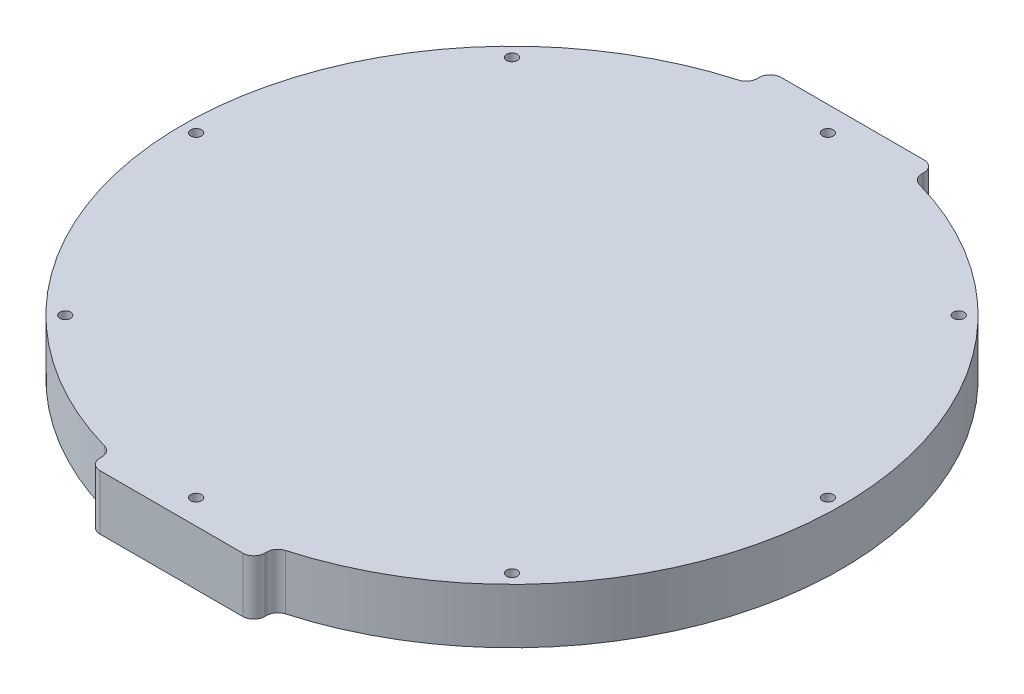
SolidWorks part; units mm, degrees
material "6061 Alloy"
ref_plane "Front Plane" through (0, 0, 0) normal (0, 0, 1) x (1, 0, 0)
ref_plane "Top Plane" through (0, 0, 0) normal (0, 1, 0) x (1, 0, 0)
ref_plane "Right Plane" through (0, 0, 0) normal (1, 0, 0) x (0, 0, -1)
sketch "Sketch2" plane through (0, 0, 0) normal (0, 1, 0) x (1, 0, 0)
  circle A0 centre (0, 0) radius 76.2
extrude "Boss-Extrude1" add sketch "Sketch2" along normal blind 12.7
sketch "Sketch3" plane through (0, 0, 0) normal (0, 0, 1) x (1, 0, 0)
  line L0 (0, 0) -> (-19.05, 0)
  line L1 (-19.05, 0) -> (-19.05, 12.7)
  line L2 (-19.05, 12.7) -> (19.05, 12.7)
  line L3 (19.05, 12.7) -> (19.05, 0)
  line L4 (0, 0) -> (19.05, 0)
extrude "Boss-Extrude2" add sketch "Sketch3" along normal blind 78.74 and the other way blind 78.74
fillet "Fillet1" radius 2.54 8 edges at (19.05, 6.35, 73.7803) (19.05, 6.35, 78.74) (-19.05, 6.35, 73.7803) (-19.05, 6.35, 78.74) (-19.05, 6.35, -73.7803) (-19.05, 6.35, -78.74) (19.05, 6.35, -73.7803) (19.05, 6.35, -78.74)
sketch "Sketch4" plane through (0, 12.7, 0) normal (0, 1, 0) x (1, 0, 0)
  circle A0 centre (73.025, 0) radius 1.2497
  circle A1 centre (51.6365, -51.6365) radius 1.2497
  circle A2 centre (0, -73.025) radius 1.2497
  circle A3 centre (-51.6365, -51.6365) radius 1.2497
  circle A4 centre (-73.025, 0) radius 1.2497
  circle A5 centre (-51.6365, 51.6365) radius 1.2497
  circle A6 centre (0, 73.025) radius 1.2497
  circle A7 centre (51.6365, 51.6365) radius 1.2497
  point P18 (0, 0)
  dimension "D1" = 8
extrude "Cut-Extrude1" cut sketch "Sketch4" against normal through all
